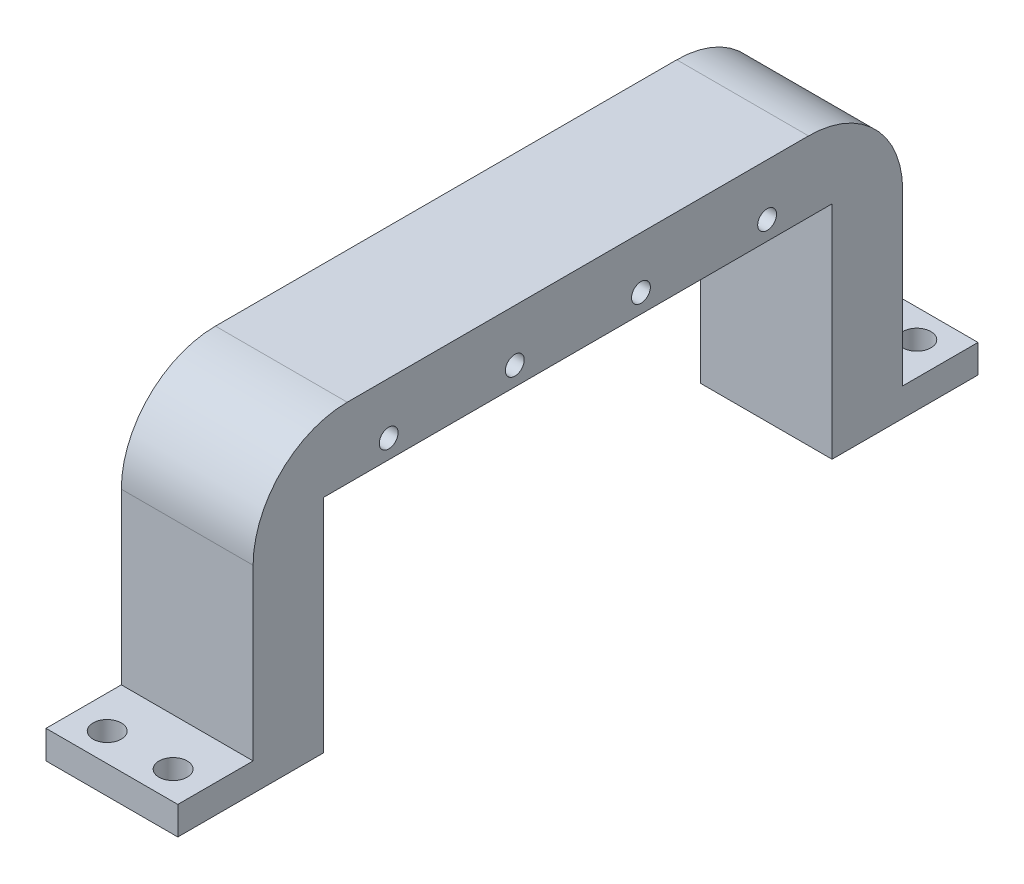
SolidWorks part; units mm, degrees
ref_plane "Front Plane" through (0, 0, 0) normal (0, 0, 1) x (1, 0, 0)
ref_plane "Top Plane" through (0, 0, 0) normal (0, 1, 0) x (1, 0, 0)
ref_plane "Right Plane" through (0, 0, 0) normal (1, 0, 0) x (0, 0, -1)
sketch "Sketch1" plane through (0, 0, 0) normal (1, 0, 0) x (0, 0, -1)
  line L0 (0, 0) -> (0, 9.568) construction
  line L1 (-27, 0) -> (27, 0)
  line L2 (27, 0) -> (27, -23.5)
  line L3 (27, -23.5) -> (34.5, -23.5)
  line L4 (34.5, -23.5) -> (34.5, 7.5)
  line L5 (34.5, 7.5) -> (-34.5, 7.5)
  line L6 (-34.5, -23.5) -> (-34.5, 7.5)
  line L7 (-27, -23.5) -> (-34.5, -23.5)
  line L8 (-27, 0) -> (-27, -23.5)
  point P9 (0, 7.5)
  dimension "D1" = 54
  dimension "D2" = 7.5
  dimension "D3" = 7.5
  dimension "D4" = 23.5
extrude "Boss-Extrude1" add sketch "Sketch1" along normal blind 7 and the other way blind 7
fillet "Fillet1" radius 10 2 edges at (0, 7.5, 34.5) (0, 7.5, -34.5)
sketch "Sketch2" plane through (7, 0, 0) normal (1, 0, 0) x (0, 0, -1)
  line L0 (0, 0) -> (0, 7.5) construction
  line L1 (24.5, 7.5) -> (-24.5, 7.5) construction
  line L2 (-27, 0) -> (27, 0) construction
  circle A0 centre (-6.7, 2) radius 1
  circle A1 centre (-20.1, 2) radius 1
  circle A2 centre (20.1, 2) radius 1
  circle A3 centre (6.7, 2) radius 1
  dimension "D4" = 2
  dimension "D5" = 2
  dimension "D1" = 2
  dimension "D2" = 6.7
  dimension "D3" = 13.4
extrude "Cut-Extrude1" cut sketch "Sketch2" against normal through all
sketch "Sketch3" plane through (0, -23.5, 0) normal (0, -1, 0) x (1, 0, 0)
  line L0 (0, -27) -> (0, -34.5) construction
  line L1 (-7, -27) -> (7, -27) construction
  line L2 (-7, -34.5) -> (7, -34.5) construction
  line L3 (-7, -30.75) -> (7, -30.75) construction
  line L4 (-7, -27) -> (-7, -34.5) construction
  line L5 (7, -27) -> (7, -34.5) construction
  line L6 (0, 0) -> (7, 0) construction
  line L7 (7, 27) -> (7, -27) construction
  circle A0 centre (-3.5, -30.75) radius 1.5
  circle A1 centre (3.5, -30.75) radius 1.5
  circle A2 centre (-3.5, 30.75) radius 1.5
  circle A3 centre (3.5, 30.75) radius 1.5
  dimension "D1" = 3
  dimension "D2" = 3.5
extrude "Cut-Extrude2" cut sketch "Sketch3" against normal blind 5
sketch "Sketch4" plane through (0, -23.5, 0) normal (0, -1, 0) x (1, 0, 0)
  line L0 (0, 0) -> (7, 0) construction
  line L1 (-7, 34.5) -> (7, 34.5)
  line L2 (-7, 34.5) -> (-7, 42.5)
  line L3 (-7, 42.5) -> (7, 42.5)
  line L4 (7, 34.5) -> (7, 42.5)
  line L5 (7, 27) -> (7, -27) construction
  line L6 (7, 34.5) -> (7, 27) construction
  line L7 (0, 39.5) -> (0, 42.5) construction
  line L8 (0, -39.5) -> (0, -42.5) construction
  line L9 (-7, -39.5) -> (7, -39.5) construction
  line L10 (7, -34.5) -> (7, -42.5)
  line L11 (-7, -42.5) -> (7, -42.5)
  line L12 (-7, -34.5) -> (-7, -42.5)
  line L13 (-7, -34.5) -> (7, -34.5)
  circle A0 centre (-3.5, 39.5) radius 1.5
  circle A1 centre (3.5, 39.5) radius 1.5
  circle A2 centre (3.5, -39.5) radius 1.5
  circle A3 centre (-3.5, -39.5) radius 1.5
  dimension "D4" = 3
  dimension "D1" = 8
  dimension "D2" = 3.5
  dimension "D3" = 3
extrude "Boss-Extrude2" add sketch "Sketch4" against normal blind 3
